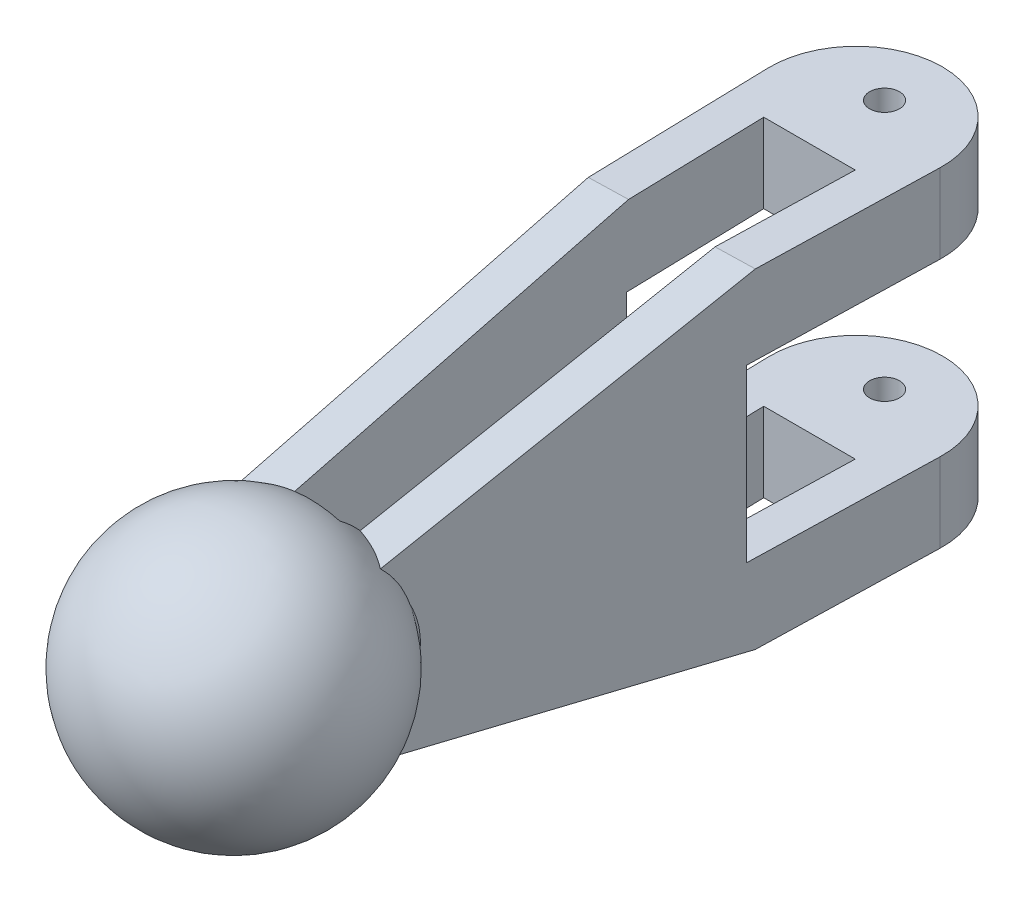
SolidWorks part; units mm, degrees
ref_plane "Front Plane" through (0, 0, 0) normal (0, 0, 1) x (1, 0, 0)
ref_plane "Top Plane" through (0, 0, 0) normal (0, 1, 0) x (1, 0, 0)
ref_plane "Right Plane" through (0, 0, 0) normal (1, 0, 0) x (0, 0, -1)
sketch "Sketch1" plane through (0, 0, 0) normal (0, 1, 0) x (1, 0, 0)
  line L0 (-13.9448, -0.3652) -> (-11.6169, -89.2652)
  line L1 (13.9448, -0.3652) -> (11.6169, -89.2652)
  line L2 (0, 15.9405) -> (0, -57.1464) construction
  arc A0 (13.9448, -0.3652) -> (-13.9448, -0.3652) centre (0, 0) ccw
  arc A1 (-11.6169, -89.2652) -> (11.6169, -89.2652) centre (0, -95.9895) ccw
  dimension "D2" = 1.5
  dimension "D3" = 1.5
  dimension "D4" = 88.9
  dimension "D5" = 88.9
extrude "Boss-Extrude1" add sketch "Sketch1" along normal blind 53.34 contours L0 A1 L1 A0
ref_plane "Plane1" through (0, 0, 0.3652) normal (0, 0, -1) x (-1, 0, 0)
sketch "Sketch2" plane through (0, 0, 0.3652) normal (0, 0, -1) x (-1, 0, 0)
  line L1 (-13.8535, 41.783) -> (16.0684, 41.783)
  line L2 (-13.8535, 41.783) -> (-13.8535, 37.211)
  line L3 (-13.8535, 37.211) -> (16.0684, 37.211)
  line L4 (16.0684, 41.783) -> (16.0684, 37.211)
  line L5 (13.4226, 53.34) -> (-13.4226, 53.34) construction
  dimension "D1" = 4.572
  dimension "D2" = 11.557
sketch "Sketch3" plane through (0, 0, 0) normal (0, -1, 0) x (1, 0, 0)
  line L0 (-5.2137, 91.2104) -> (-7.404, 7.5684)
  line L1 (7.404, 7.5684) -> (5.2137, 91.2104)
  line L2 (13.9448, 0.3652) -> (11.6169, 89.2652)
  line L3 (-11.6169, 89.2652) -> (-13.9448, 0.3652)
  line L4 (13.9448, 0.3652) -> (11.6169, 89.2652)
  line L5 (-11.6169, 89.2652) -> (-13.9448, 0.3652)
  line L6 (7.404, 7.5684) -> (-11.1568, 7.5684)
  line L7 (7.597, 0.1989) -> (5.2137, 91.2104) construction
  line L8 (-5.2137, 91.2104) -> (-7.597, 0.1989) construction
  arc A2 (-13.9448, 0.3652) -> (13.9448, 0.3652) centre (0, 0) ccw
  arc A3 (11.6169, 89.2652) -> (-11.6169, 89.2652) centre (0, 95.9895) ccw
  arc A4 (-13.9448, 0.3652) -> (13.9448, 0.3652) centre (0, 0) ccw
  arc A5 (11.6169, 89.2652) -> (-11.6169, 89.2652) centre (0, 95.9895) ccw
  arc A7 (5.2137, 91.2104) -> (-5.2137, 91.2104) centre (0, 95.9895) ccw construction
  arc A8 (5.2137, 91.2104) -> (-5.2137, 91.2104) centre (0, 97.3127) ccw
  arc A10 (-7.597, 0.1989) -> (7.597, 0.1989) centre (0, 0) ccw construction
  dimension "D1" = 0
  dimension "D2" = 6.35
sketch "Sketch4" plane through (13.9448, 0, 0.3652) normal (0.9997, 0, 0.0262) x (0.0262, 0, -0.9997)
  line L0 (0, 53.34) -> (0, 0) construction
  line L1 (-30.5363, 12.827) -> (30.5363, 12.827)
  line L2 (-30.5363, 12.827) -> (-30.5363, 40.513)
  line L3 (-30.5363, 40.513) -> (30.5363, 40.513)
  line L4 (30.5363, 12.827) -> (30.5363, 40.513)
  line L5 (-30.5363, 12.827) -> (30.5363, 40.513) construction
  line L6 (-30.5363, 40.513) -> (30.5363, 12.827) construction
  point P0 (0, 26.67)
  dimension "D1" = 27.686
extrude "Cut-Extrude3" cut sketch "Sketch4" against normal through all
sketch "Sketch5" plane through (0, 53.34, 0) normal (0, 1, 0) x (1, 0, 0)
  line L0 (7.404, -7.5684) -> (5.2137, -91.2104) construction
  line L1 (-5.2137, -91.2104) -> (-7.404, -7.5684) construction
  line L2 (-13.9448, -0.3652) -> (-11.6169, -89.2652)
  line L3 (11.6169, -89.2652) -> (13.9448, -0.3652)
  line L4 (-13.9448, -0.3652) -> (-11.6169, -89.2652)
  line L5 (11.6169, -89.2652) -> (13.9448, -0.3652)
  line L6 (7.404, -7.5684) -> (-11.1568, -7.5684) construction
  line L7 (7.404, -7.5684) -> (5.2137, -91.2104)
  line L8 (-5.2137, -91.2104) -> (-7.404, -7.5684)
  line L9 (7.404, -7.5684) -> (-7.404, -7.5684)
  arc A0 (-5.2137, -91.2104) -> (5.2137, -91.2104) centre (0, -97.3127) ccw construction
  arc A1 (-5.2137, -91.2104) -> (5.2137, -91.2104) centre (0, -97.3127) ccw
  arc A2 (13.9448, -0.3652) -> (-13.9448, -0.3652) centre (0, 0) ccw
  arc A3 (-11.6169, -89.2652) -> (11.6169, -89.2652) centre (0, -95.9895) ccw
  arc A4 (13.9448, -0.3652) -> (-13.9448, -0.3652) centre (0, 0) ccw
  arc A5 (-11.6169, -89.2652) -> (11.6169, -89.2652) centre (0, -95.9895) ccw
  dimension "D1" = 0
extrude "Cut-Extrude5" cut sketch "Sketch5" against normal through all flip side to cut
sketch "Sketch6" plane through (0, 53.34, 0) normal (0, 1, 0) x (1, 0, 0)
  circle A0 centre (0, 4.5787) radius 2.413
  dimension "D1" = 4.826
extrude "Cut-Extrude6" cut sketch "Sketch6" against normal through all
sketch "Sketch7" plane through (-13.9448, 0, 0.3652) normal (-0.9997, 0, 0.0262) x (0.0262, 0, 0.9997)
  line L0 (88.9305, 26.67) -> (-49.4986, 26.67) construction
  line L2 (88.9305, 26.67) -> (88.9305, 40.09)
  line L3 (88.9305, 53.34) -> (88.9305, 0) construction
  line L4 (88.9305, 26.67) -> (88.9305, 13.25)
  line L5 (29.8472, 12.827) -> (29.8472, 0)
  line L6 (0, 0) -> (88.9305, 0) construction
  line L7 (29.8472, 40.513) -> (29.8472, 53.34)
  line L8 (0, 53.34) -> (88.9305, 53.34) construction
  line L9 (29.8472, 0) -> (88.9305, 13.25)
  line L10 (29.8472, 53.34) -> (88.9305, 40.09)
  line L11 (29.8472, 53.34) -> (138.7027, 53.34)
  line L12 (138.7027, 53.34) -> (138.7027, 0)
  line L13 (138.7027, 0) -> (29.8472, 0)
  line L14 (88.9305, 13.25) -> (115.1967, 13.25)
  line L15 (115.1967, 13.25) -> (115.1967, 40.09)
  line L16 (115.1967, 40.09) -> (88.9305, 40.09)
  line M7 (0, 0) -> (88.9305, 0)
  line M8 (88.9305, 0) -> (88.9305, 53.34)
  line M9 (88.9305, 53.34) -> (0, 53.34)
  dimension "D1" = 13.42
  dimension "D2" = 13.42
extrude "Cut-Extrude8" cut sketch "Sketch7" against normal blind 100 and the other way blind 100 contours L12 L0 L15 L14 L13 M8 | L0 L12 L11 L16 L15 M8 | L10 M9 M8 | L9 M7 M8 region at (-10.8542, 26.67, 118.3907) region at (-12.1324, 48.9233, 69.5775) region at (-12.1324, 4.4167, 69.5775)
sketch "Sketch8" plane through (0, 40.09, 0) normal (0, 1, 0) x (1, 0, 0)
  line L0 (-11.6169, -89.2652) -> (19.7485, -88.4438)
  line L1 (19.7485, -88.4438) -> (21.1363, -119.7324)
  line L2 (21.1363, -119.7324) -> (-27.7693, -116.2194)
  line L3 (-27.7693, -116.2194) -> (-20.4659, -89.2652)
  line L4 (-20.4659, -89.2652) -> (-11.6169, -89.2652)
extrude "Cut-Extrude9" cut sketch "Sketch8" against normal blind 100
ref_plane "Plane2" through (0, 0, 0) normal (-1, 0, 0) x (0, 0, 1)
sketch "Sketch12" plane through (2.3279, 0, 88.9) normal (0.0262, 0, 0.9997) x (0.9997, 0, -0.0262)
  line L0 (-13.9496, 40.09) -> (-7.5996, 13.4527)
  line L1 (-7.5996, 40.09) -> (-7.5996, 13.25) construction
  line L2 (-13.9496, 13.25) -> (-7.5996, 40.09)
  line L5 (-10.7746, 26.7713) -> (-13.9496, 26.7713)
  line L6 (-13.9496, 40.09) -> (-13.9496, 13.25) construction
ref_plane "Plane4" through (0, 26.7713, 0) normal (0, 1, 0) x (-0.9997, 0, 0.0262)
sketch "Sketch18" plane through (2.3279, 0, 88.9) normal (0.0262, 0, 0.9997) x (0.9997, 0, -0.0262)
  line L0 (9.3081, 13.25) -> (9.3081, 40.09) construction
  line L1 (9.3081, 26.67) -> (-13.9496, 26.7713)
  circle A0 centre (-2.3208, 26.7207) radius 17.7191
sketch "Sketch14" plane through (0, 26.7713, 0) normal (0, 1, 0) x (-0.9997, 0, 0.0262)
  line L2 (2.3208, 44.2132) -> (2.3208, 122.5564) construction
  line L3 (20.0399, 88.9305) -> (-15.3984, 88.9305) construction
  line L4 (7.5996, 88.9305) -> (2.3208, 88.9305)
  line L5 (7.5996, 88.9305) -> (7.5996, 74.6994)
  line L7 (7.5996, 74.6994) -> (15.6499, 84.2289)
  line L8 (7.5996, 88.9305) -> (7.5996, 29.8472) construction
  line L9 (2.3208, 88.9305) -> (2.3208, 122.5564)
  arc A0 (15.6499, 84.2289) -> (2.3208, 122.5564) centre (2.3208, 101.0749) ccw
  point P4 (6.9767, 75.5467)
  point P12 (7.5996, 74.6994)
revolve "Revolve2" add sketch "Sketch14" angle 360 about L2
sketch "Sketch21" plane through (0, 26.7713, 0) normal (0, 1, 0) x (-0.9997, 0, 0.0262)
  line L0 (7.5996, 74.6994) -> (-3.6952, 74.6994)
  line L1 (-6.0458, 29.8472) -> (-2.9493, 88.9305) construction
  line L2 (7.5996, 74.6994) -> (7.5996, 88.9305)
  line L3 (7.5996, 88.9305) -> (-2.9493, 88.9305)
  line L4 (-3.6952, 74.6994) -> (-2.9493, 88.9305)
  point P5 (-3.3222, 88.9305)
extrude "Cut-Extrude10" cut sketch "Sketch21" against normal through all both and the other way through all
